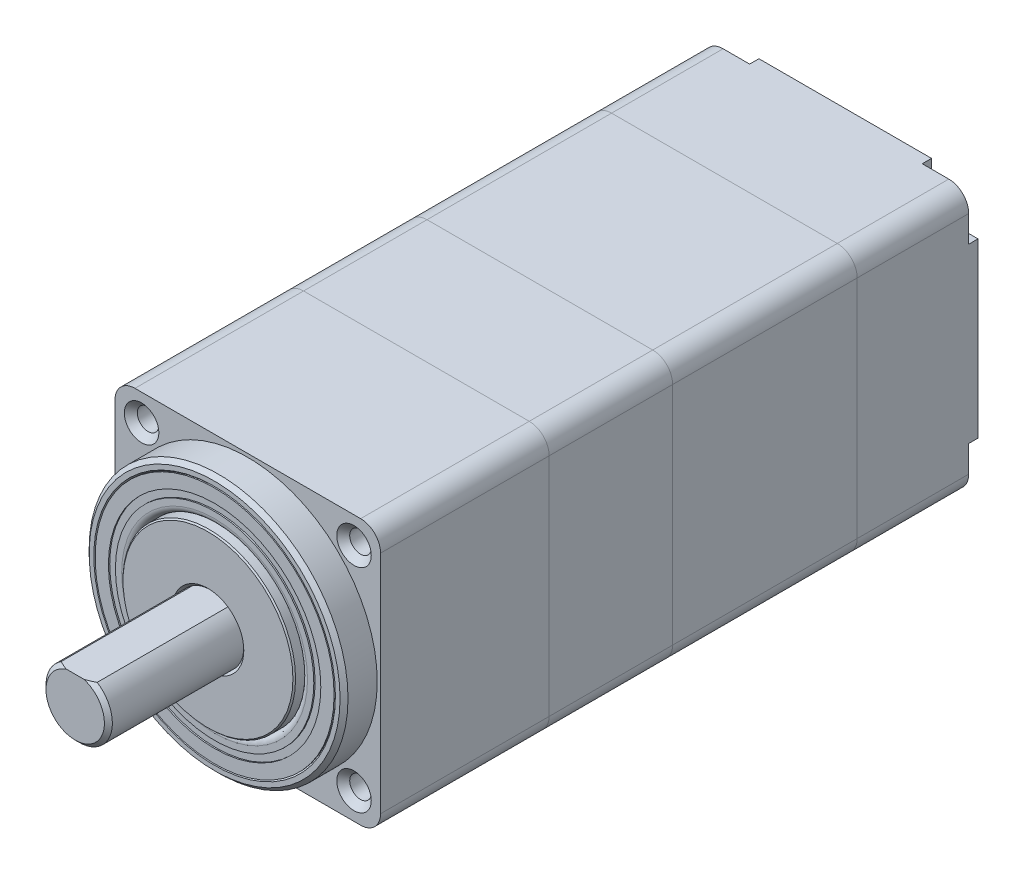
SolidWorks part; units mm, degrees
ref_plane "前视基准面" through (0, 0, 0) normal (0, 0, 1) x (1, 0, 0)
ref_plane "上视基准面" through (0, 0, 0) normal (0, 1, 0) x (1, 0, 0)
ref_plane "右视基准面" through (0, 0, 0) normal (1, 0, 0) x (0, 0, -1)
other "Configuration Table"
sketch "草图1" plane through (0, 0, 0) normal (0, 0, 1) x (1, 0, 0)
  line L1 (-10, 10) -> (10, 10)
  line L2 (-10, 10) -> (-10, -10)
  line L3 (-10, -10) -> (10, -10)
  line L4 (10, 10) -> (10, -10)
  line L5 (-10, 10) -> (10, -10) construction
  line L6 (-10, -10) -> (10, 10) construction
  point P0 (0, 0)
  dimension "D1" = 20
  dimension "D2" = 20
extrude "凸台-拉伸1" add sketch "草图1" along normal blind 9.1
sketch "草图2" plane through (0, 0, 0) normal (0, 0, -1) x (-1, 0, 0)
  line L1 (8, -8) -> (-8, -8) construction
  line L2 (8, -8) -> (8, 8) construction
  line L3 (8, 8) -> (-8, 8) construction
  line L4 (-8, -8) -> (-8, 8) construction
  line L5 (8, -8) -> (-8, 8) construction
  line L6 (8, 8) -> (-8, -8) construction
  circle A0 centre (-8, 8) radius 1
  circle A1 centre (8, 8) radius 1
  circle A2 centre (8, -8) radius 1
  circle A3 centre (-8, -8) radius 1
  point P0 (0, 0)
  dimension "D2" = 2
  dimension "D1" = 16
extrude "切除-拉伸1" cut sketch "草图2" against normal up to next
sketch "草图3" plane through (0, 0, 0) normal (0, 0, -1) x (-1, 0, 0)
  line L1 (-10, 10) -> (-6.5, 10)
  line L2 (-10, 10) -> (-10, 6.5)
  line L3 (-10, 6.5) -> (-6.5, 6.5)
  line L4 (-6.5, 10) -> (-6.5, 6.5)
  line L5 (10, 10) -> (6.5, 10)
  line L6 (10, 10) -> (10, 6.5)
  line L7 (10, 6.5) -> (6.5, 6.5)
  line L8 (6.5, 10) -> (6.5, 6.5)
  line L9 (10, -10) -> (6.5, -10)
  line L10 (10, -10) -> (10, -6.5)
  line L11 (10, -6.5) -> (6.5, -6.5)
  line L12 (6.5, -10) -> (6.5, -6.5)
  line L13 (-10, -10) -> (-6.5, -10)
  line L14 (-10, -10) -> (-10, -6.5)
  line L15 (-10, -6.5) -> (-6.5, -6.5)
  line L16 (-6.5, -10) -> (-6.5, -6.5)
  dimension "D1" = 3.5
extrude "切除-拉伸2" cut sketch "草图3" against normal blind 0.7
fillet "圆角1" radius 1.5 4 edges at (-6.5, -6.5, 0.35) (6.5, -6.5, 0.35) (-6.5, 6.5, 0.35) (6.5, 6.5, 0.35)
sketch "草图12" plane through (0, 0, 0) normal (0, 0, -1) x (-1, 0, 0)
  circle A0 centre (0, 0) radius 2.5
  dimension "D1" = 5
extrude "切除-拉伸6" cut sketch "草图12" against normal blind 4
sketch "草图4" plane through (0, 0, 9.1) normal (0, 0, 1) x (1, 0, 0)
  line L4 (10, -10) -> (10, 10)
  line L5 (10, 10) -> (-10, 10)
  line L6 (-10, 10) -> (-10, -10)
  line L7 (-10, -10) -> (10, -10)
  line L8 (10, -10) -> (10, 10)
  line L9 (10, 10) -> (-10, 10)
  line L10 (-10, 10) -> (-10, -10)
  line L11 (-10, -10) -> (10, -10)
  dimension "D1" = 0
extrude "凸台-拉伸2" add sketch "草图4" along normal blind 13.9 separate body
sketch "草图5" plane through (0, 0, 23) normal (0, 0, 1) x (1, 0, 0)
  line L4 (-10, -10) -> (10, -10)
  line L5 (10, -10) -> (10, 10)
  line L6 (10, 10) -> (-10, 10)
  line L7 (-10, 10) -> (-10, -10)
  line L8 (-10, -10) -> (10, -10)
  line L9 (10, -10) -> (10, 10)
  line L10 (10, 10) -> (-10, 10)
  line L11 (-10, 10) -> (-10, -10)
  dimension "D1" = 0
extrude "凸台-拉伸3" add sketch "草图5" along normal blind 9.3 separate body
sketch "草图7" plane through (0, 0, 32.3) normal (0, 0, 1) x (1, 0, 0)
  line L4 (-10, 10) -> (-10, -10)
  line L5 (-10, -10) -> (10, -10)
  line L6 (10, -10) -> (10, 10)
  line L7 (10, 10) -> (-10, 10)
  line L8 (-10, 10) -> (-10, -10)
  line L9 (-10, -10) -> (10, -10)
  line L10 (10, -10) -> (10, 10)
  line L11 (10, 10) -> (-10, 10)
  dimension "D1" = 0
extrude "凸台-拉伸4" add sketch "草图7" along normal blind 12.7 separate body
sketch "草图8" plane through (0, 0, 45) normal (0, 0, 1) x (1, 0, 0)
  line L1 (8, -8) -> (-8, -8) construction
  line L2 (8, -8) -> (8, 8) construction
  line L3 (8, 8) -> (-8, 8) construction
  line L4 (-8, -8) -> (-8, 8) construction
  line L5 (8, -8) -> (-8, 8) construction
  line L6 (8, 8) -> (-8, -8) construction
  circle A0 centre (-8, 8) radius 0.8115
  circle A1 centre (8, 8) radius 0.8115
  circle A2 centre (8, -8) radius 0.8115
  circle A3 centre (-8, -8) radius 0.8115
  point P0 (0, 0)
  dimension "D1" = 1.623
  dimension "D2" = 16
extrude "切除-拉伸4" cut sketch "草图8" against normal up to next (12.7 mm away)
fillet "圆角2" radius 1.5 4 edges at (10, -10, 38.65) (-10, -10, 38.65) (-10, 10, 38.65) (10, 10, 38.65)
fillet "圆角3" radius 1.5 4 edges at (-10, -10, 27.65) (10, -10, 27.65) (-10, 10, 27.65) (10, 10, 27.65)
fillet "圆角4" radius 1.5 4 edges at (-10, -10, 16.05) (10, -10, 16.05) (-10, 10, 16.05) (10, 10, 16.05)
fillet "圆角5" radius 1.5 4 edges at (10, -10, 4.9) (-10, -10, 4.9) (-10, 10, 4.9) (10, 10, 4.9)
chamfer "倒角2" distance 0.4885 angle 45 1 edges at (8.8115, 8, 45)
sketch "草图13" plane through (0, 0, 45) normal (0, 0, 1) x (1, 0, 0)
  circle A0 centre (0, 0) radius 9.75
  circle A1 centre (0, 0) radius 9
  dimension "D1" = 19.5
  dimension "D2" = 18
extrude "凸台-拉伸5" add sketch "草图13" along normal blind 2.5 separate body
chamfer "倒角3" distance 0.3 angle 45 1 edges at (9.75, 0, 47.5)
chamfer "倒角4" distance 0.1 angle 45 1 edges at (9, 0, 47.5)
sketch "草图14" plane through (0, 0, 45) normal (0, 0, 1) x (1, 0, 0)
  circle A0 centre (0, 0) radius 6.5
  circle A1 centre (0, 0) radius 2.5
  dimension "D1" = 13
  dimension "D2" = 5
extrude "凸台-拉伸6" add sketch "草图14" along normal blind 3 separate body
chamfer "倒角5" distance 0.1 angle 45 1 edges at (6.5, 0, 48)
chamfer "倒角6" distance 0.2 angle 45 1 edges at (2.5, 0, 48)
sketch "草图15" plane through (0, 0, 45) normal (0, 0, 1) x (1, 0, 0)
  circle A0 centre (0, 0) radius 9
  circle A1 centre (0, 0) radius 6.5
  dimension "D1" = 18
  dimension "D2" = 13
extrude "凸台-拉伸7" add sketch "草图15" along normal blind 2.5 separate body
fillet "圆角6" radius 0.5 1 edges at (6.5, 0, 47.5)
sketch "草图16" plane through (0, 0, 47.5) normal (0, 0, 1) x (1, 0, 0)
  circle A0 centre (0, 0) radius 7.4725
  circle A1 centre (0, 0) radius 8
  dimension "D1" = 14.945
  dimension "D2" = 16
extrude "切除-拉伸7" cut sketch "草图16" against normal blind 0.1
sketch "草图17" plane through (0, 0, 45) normal (0, 0, 1) x (1, 0, 0)
  circle A0 centre (0, 0) radius 2.5
  dimension "D1" = 5
extrude "凸台-拉伸8" add sketch "草图17" along normal blind 13 separate body
sketch "草图18" plane through (0, 0, 58) normal (0, 0, 1) x (1, 0, 0)
  line L0 (-1.3565, 2.1) -> (1.3565, 2.1)
  circle A1 centre (0, 0) radius 2.5
  arc A2 (1.3565, 2.1) -> (-1.3565, 2.1) centre (0, 0) ccw
  dimension "D2" = 2.1
  dimension "D1" = 0
extrude "切除-拉伸8" cut sketch "草图18" against normal up to next (13 mm away)
chamfer "倒角7" distance 0.3 angle 45 1 edges at (0, -2.5, 58)
